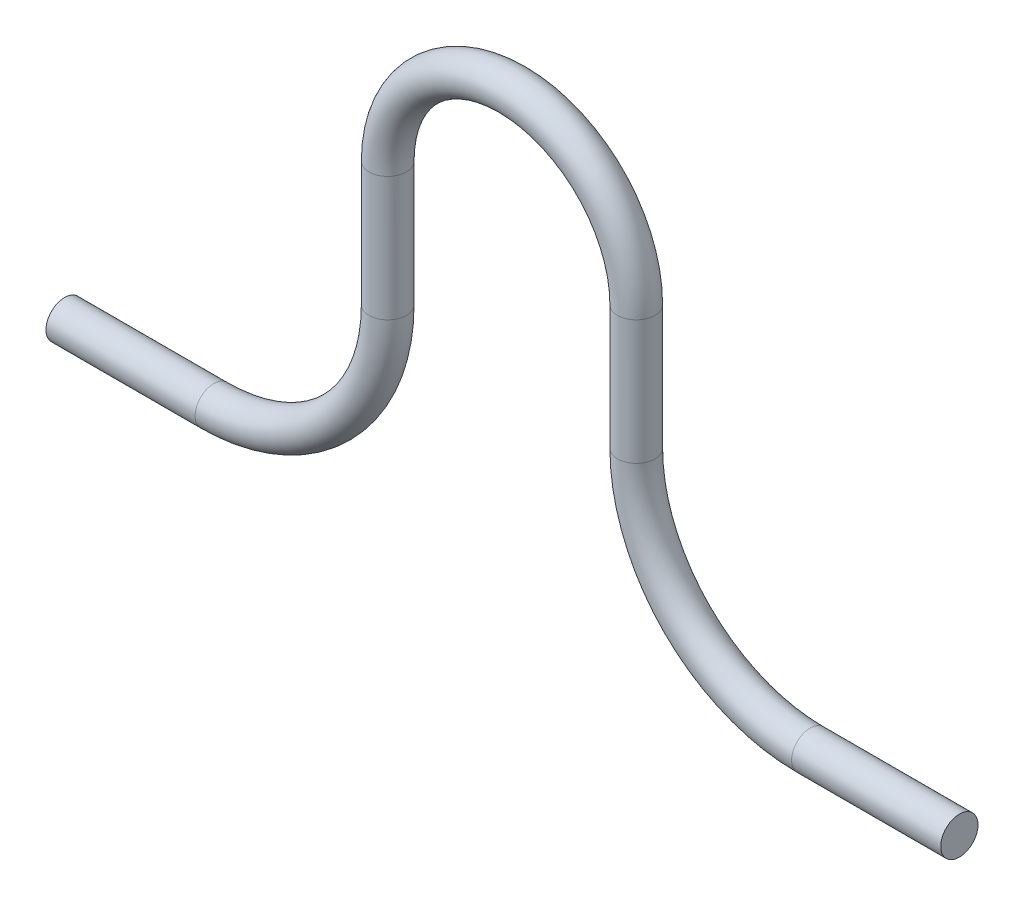
SolidWorks part; units mm, degrees
material "Ст 3 ГОСТ 380-88"
ref_plane "Спереди" through (0, 0, 0) normal (0, 0, 1) x (1, 0, 0)
ref_plane "Сверху" through (0, 0, 0) normal (0, 1, 0) x (1, 0, 0)
ref_plane "Справа" through (0, 0, 0) normal (1, 0, 0) x (0, 0, -1)
sketch "Эскиз1" plane through (0, 0, 0) normal (0, 0, 1) x (1, 0, 0)
  line L0 (-270, -100) -> (-157.5, -100)
  line L1 (-150, -92.5) -> (-150, -7.5)
  line L2 (-142.5, 0) -> (0, 0)
  line L3 (0, -32.2292) -> (0, 86.8288) construction
  arc A0 (-142.5, 0) -> (-150, -7.5) centre (-142.5, -7.5) ccw
  arc A1 (-150, -92.5) -> (-157.5, -100) centre (-157.5, -92.5) cw
  point P10 (-150, 0)
  point P13 (-150, -100)
  point P15 (0, 30)
  dimension "D4" = 7.5
  dimension "D1" = 120
  dimension "D2" = 100
  dimension "D3" = 150
sketch "Эскиз3" plane through (0, 0, 0) normal (1, 0, 0) x (0, 0, -1)
  circle A0 centre (0, 0) radius 7.5
  dimension "D1" = 15
sketch "Эскиз4" plane through (0, 0, 0) normal (0, 0, 1) x (1, 0, 0)
  line L0 (-50, -50) -> (-50, -100)
  line L2 (-142.5, 0) -> (0, 0) construction
  line L3 (-180, -170) -> (-120, -170)
  line L4 (0, 175.2203) -> (0, -194.0851) construction
  arc A0 (-50, -100) -> (-120, -170) centre (-120, -100) cw
  arc A3 (-50, -50) -> (0, 0) centre (0, -50) cw
  dimension "D1" = 50
  dimension "D2" = 50
  dimension "D4" = 70
  dimension "D3" = 60
sketch "Эскиз5" plane through (0, 0, 0) normal (1, 0, 0) x (0, 0, -1)
  circle A1 centre (0, 0) radius 7.5
  circle A2 centre (0, 0) radius 7.5
  dimension "D1" = 0
sweep "По траектории3" add profiles "Эскиз5" path "Эскиз4"
mirror "Зеркальное отражение4" about plane through (0, 0, 0) normal (1, 0, 0) of "По траектории3"
ref_axis "Ось1" through (202.5829, -170, 0) along (-1, 0, 0)
